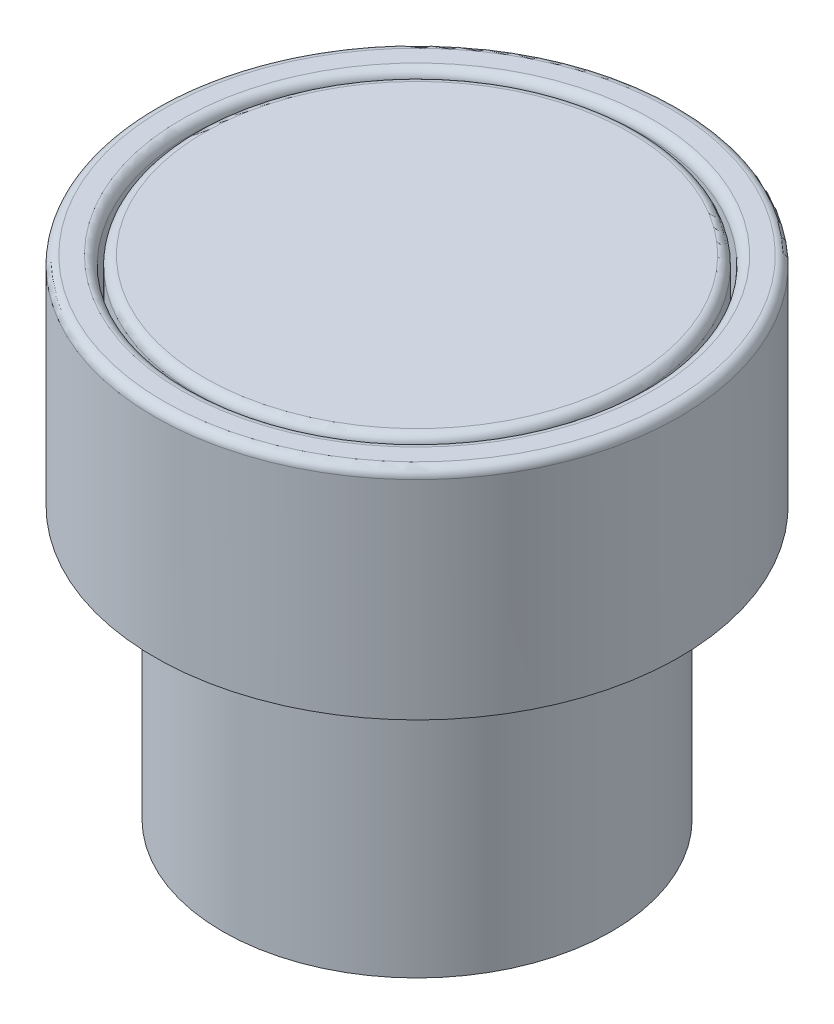
SolidWorks part; units mm, degrees
ref_plane "Front Plane" through (0, 0, 0) normal (0, 0, 1) x (1, 0, 0)
ref_plane "Top Plane" through (0, 0, 0) normal (0, 1, 0) x (1, 0, 0)
ref_plane "Right Plane" through (0, 0, 0) normal (1, 0, 0) x (0, 0, -1)
sketch "Sketch1" plane through (0, 0, 0) normal (0, 1, 0) x (1, 0, 0)
  circle A0 centre (0, 0) radius 14.5
  circle A1 centre (0, 0) radius 12.5
  dimension "D1" = 29
  dimension "D2" = 25
extrude "Boss-Extrude1" add sketch "Sketch1" along normal blind 11
sketch "Sketch2" plane through (0, 0, 0) normal (0, -1, 0) x (-1, 0, 0)
  circle A0 centre (0, 0) radius 14.5
extrude "Boss-Extrude2" add sketch "Sketch2" along normal blind 1
sketch "Sketch3" plane through (0, -1, 0) normal (0, -1, 0) x (1, 0, 0)
  circle A0 centre (0, 0) radius 10.75
  dimension "D1" = 21.5
extrude "Boss-Extrude3" add sketch "Sketch3" along normal blind 15
sketch "Sketch4" plane through (0, 0, 0) normal (0, 1, 0) x (1, 0, 0)
  circle A0 centre (0, 0) radius 12.25
  dimension "D1" = 24.5
extrude "Boss-Extrude4" add sketch "Sketch4" along normal up to surface (11 mm away) up to face at (0, 11, 14.5)
fillet "Fillet1" radius 0.5 3 edges at (0, 11, 12.25) (0, 11, 14.5) (0, 11, 12.5)
